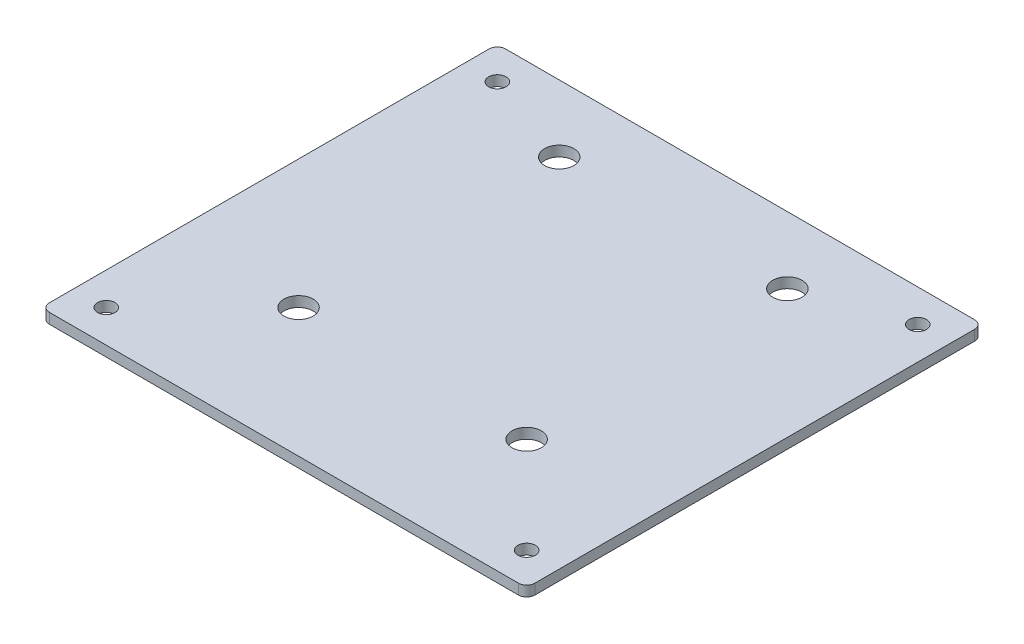
SolidWorks part; units mm, degrees
ref_plane "Front Plane" through (0, 0, 0) normal (0, 0, 1) x (1, 0, 0)
ref_plane "Top Plane" through (0, 0, 0) normal (0, 1, 0) x (1, 0, 0)
ref_plane "Right Plane" through (0, 0, 0) normal (1, 0, 0) x (0, 0, -1)
sketch "Sketch1" plane through (0, 0, 0) normal (0, 1, 0) x (1, 0, 0)
  line L1 (74.5, 70) -> (-74.5, 70)
  line L2 (74.5, 70) -> (74.5, -70)
  line L3 (74.5, -70) -> (-74.5, -70)
  line L4 (-74.5, 70) -> (-74.5, -70)
  line L5 (74.5, 70) -> (-74.5, -70) construction
  line L6 (74.5, -70) -> (-74.5, 70) construction
  point P0 (0, 0)
  dimension "D1" = 140
  dimension "D2" = 149
extrude "Boss-Extrude1" add sketch "Sketch1" along normal blind 3.175
sketch "Sketch2" plane through (0, 3.175, 0) normal (0, 1, 0) x (1, 0, 0)
  circle A0 centre (-35, 49.5) radius 4.5
  circle A1 centre (-35, -30.5) radius 4.5
  circle A2 centre (35, -30.5) radius 4.5
  circle A4 centre (35, 49.5) radius 4.5
extrude "Cut-Extrude1" cut sketch "Sketch2" against normal up to next
sketch "Sketch3" plane through (0, 3.175, 0) normal (0, 1, 0) x (-1, 0, 0)
  line L0 (64.5, -70) -> (64.5, 70) construction
  line L1 (-74.5, -70) -> (74.5, -70) construction
  line L2 (74.5, 70) -> (-74.5, 70) construction
  line L3 (74.5, 60) -> (-74.5, 60) construction
  line L4 (74.5, -70) -> (74.5, 70) construction
  line L5 (-74.5, 70) -> (-74.5, -70) construction
  line L6 (-64.5, -70) -> (-64.5, 70) construction
  circle A0 centre (64.5, 60) radius 2.665
  circle A1 centre (-64.5, 60) radius 2.665
  circle A2 centre (-64.5, -60) radius 2.665
  circle A3 centre (64.5, -60) radius 2.665
  dimension "D4" = 10
  dimension "D5" = 10
  dimension "D6" = 5.33
  dimension "D1" = 10
  dimension "D2" = 10
  dimension "D3" = 10
extrude "Cut-Extrude2" cut sketch "Sketch3" against normal up to next
fillet "Fillet1" radius 2.54 4 edges at (-74.5, 1.5875, -70) (74.5, 1.5875, -70) (74.5, 1.5875, 70) (-74.5, 1.5875, 70)
